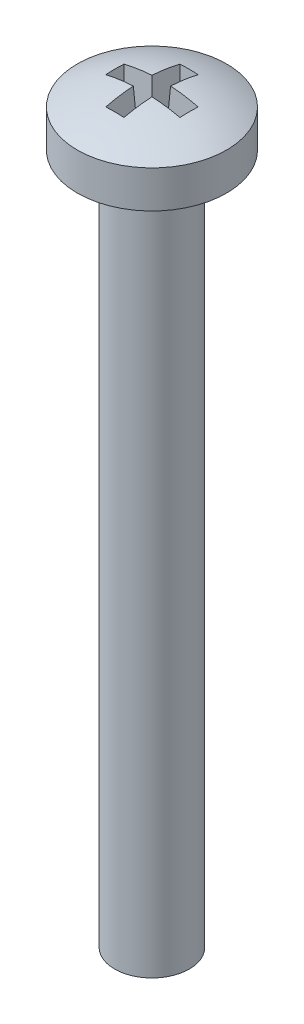
SolidWorks part; units mm, degrees
ref_plane "Front Plane" through (0, 0, 0) normal (0, 0, 1) x (1, 0, 0)
ref_plane "Top Plane" through (0, 0, 0) normal (0, 1, 0) x (1, 0, 0)
ref_plane "Right Plane" through (0, 0, 0) normal (1, 0, 0) x (0, 0, -1)
sketch "Sketch1" plane through (0, 0, 0) normal (0, 1, 0) x (1, 0, 0)
  circle A0 centre (0, 0) radius 2
  dimension "D1" = 4
extrude "Boss-Extrude1" add sketch "Sketch1" along normal blind 37
sketch "Sketch2" plane through (0, 37, 0) normal (0, 1, 0) x (1, 0, 0)
  circle A0 centre (0, 0) radius 4
  dimension "D1" = 8
extrude "Boss-Extrude2" add sketch "Sketch2" along normal blind 2
dome "Dome1" faces to dome 1 distance 1 reverse direction no elliptical dome no face at (0, 39, 4) parameters "D1"=1
ref_plane "Plane1" through (0, 40, 0) normal (0, -1, 0) x (-1, 0, 0)
sketch "Sketch4" plane through (0, 40, 0) normal (0, -1, 0) x (-1, 0, 0)
  line L0 (-0.5, 0.5) -> (-2, 0.5)
  line L1 (0.5, -2) -> (-0.5, -2)
  line L2 (0.5, -2) -> (0.5, -0.5)
  line L3 (0.5, 2) -> (-0.5, 2)
  line L4 (-0.5, -2) -> (-0.5, -0.5)
  line L5 (0.5, -2) -> (-0.5, 2) construction
  line L6 (0.5, 2) -> (-0.5, -2) construction
  line L7 (2, -0.5) -> (0.5, -0.5)
  line L8 (2, -0.5) -> (2, 0.5)
  line L9 (2, 0.5) -> (0.5, 0.5)
  line L10 (-2, -0.5) -> (-2, 0.5)
  line L11 (2, -0.5) -> (-2, 0.5) construction
  line L12 (2, 0.5) -> (-2, -0.5) construction
  line L13 (-0.5, 0.5) -> (-0.5, 2)
  line L14 (-0.5, -0.5) -> (-2, -0.5)
  line L15 (0.5, 0.5) -> (0.5, 2)
  point P0 (0, 0)
  point P6 (0, 0)
  dimension "D1" = 1
  dimension "D2" = 4
  dimension "D3" = 4
  dimension "D4" = 1
extrude "Cut-Extrude1" cut sketch "Sketch4" along normal blind 3 draft 3
